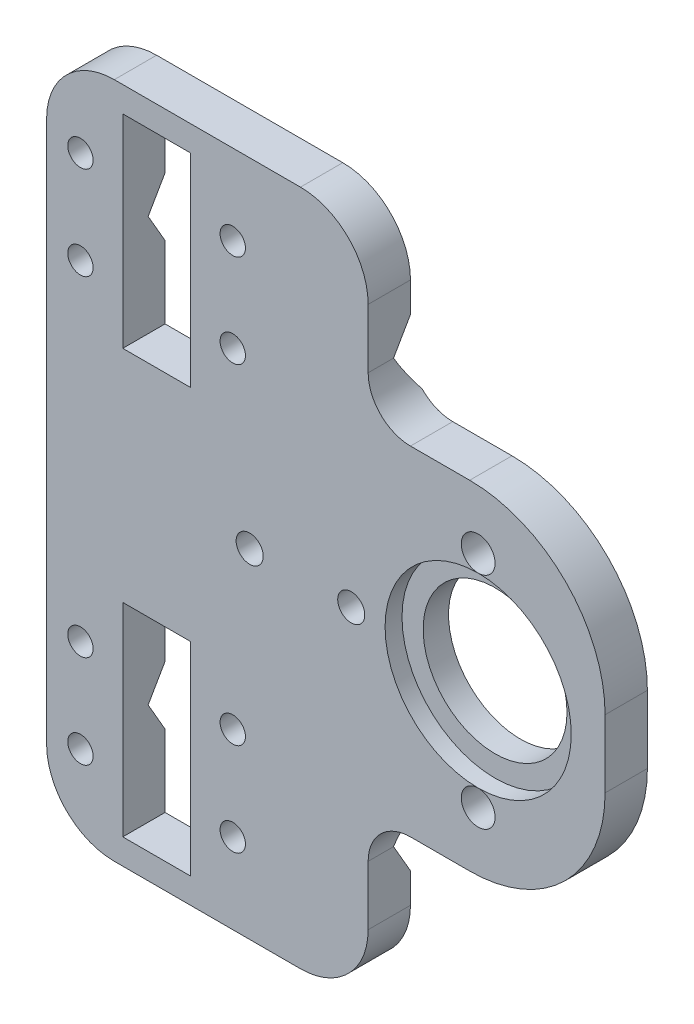
SolidWorks part; units mm, degrees
note: The reader was unsure of these and kept them because the rebuilt part matched: shared geometry of "Esboço6<3>".
material "Liga 1060"
ref_plane "Plano frontal" through (0, 0, 0) normal (0, 0, 1) x (1, 0, 0)
ref_plane "Plano superior" through (0, 0, 0) normal (0, 1, 0) x (1, 0, 0)
ref_plane "Plano direito" through (0, 0, 0) normal (1, 0, 0) x (0, 0, -1)
sketch "Esboço1" plane through (0, 0, 0) normal (0, 0, 1) x (1, 0, 0)
  line L0 (0, 0) -> (19, 0) construction
  line L1 (-19, 40) -> (19, 40)
  line L2 (-19, 40) -> (-19, -40)
  line L3 (-19, -40) -> (19, -40)
  line L4 (19, 40) -> (19, -40)
  line L5 (-19, 40) -> (19, -40) construction
  line L6 (-19, -40) -> (19, 40) construction
  line L7 (-10, 37) -> (-2, 37)
  line L8 (-10, 37) -> (-10, 13)
  line L9 (-10, 13) -> (-2, 13)
  line L10 (-2, 37) -> (-2, 13)
  line L11 (-10, 37) -> (-2, 13) construction
  line L12 (-10, 13) -> (-2, 37) construction
  line L13 (-10, -13) -> (-2, -37) construction
  line L14 (-10, -37) -> (-2, -13) construction
  line L15 (-2, -37) -> (-2, -13)
  line L16 (-10, -13) -> (-2, -13)
  line L17 (-10, -37) -> (-10, -13)
  line L18 (-10, -37) -> (-2, -37)
  line L21 (-6, 25) -> (-6, 13) construction
  line L22 (-20.4945, 25) -> (6.394, 25) construction
  line L23 (47, 20) -> (19, 20)
  line L24 (47, 20) -> (47, -20)
  line L25 (47, -20) -> (19, -20)
  line L26 (19, 20) -> (19, -20)
  line L27 (47, 20) -> (19, -20) construction
  line L28 (47, -20) -> (19, 20) construction
  circle A0 centre (-15, 19.5) radius 1.5
  circle A1 centre (-15, -19.5) radius 1.5
  circle A2 centre (3, -19.5) radius 1.5
  circle A3 centre (3, 19.5) radius 1.5
  circle A4 centre (3, 30.5) radius 1.5
  circle A5 centre (-15, 30.5) radius 1.5
  circle A6 centre (3, -30.5) radius 1.5
  circle A7 centre (-15, -30.5) radius 1.5
  point P0 (0, 0)
  point P5 (-6, 25)
  point P17 (-6, -25)
  point P30 (33, 0)
  dimension "D7" = 3
  dimension "D8" = 28
  dimension "D10" = 11
  dimension "D11" = 18
  dimension "D1" = 80
  dimension "D2" = 38
  dimension "D3" = 8
  dimension "D4" = 24
  dimension "D5" = 25
  dimension "D6" = 13
  dimension "D9" = 40
extrude "Ressalto-extrusão1" add sketch "Esboço1" along normal blind 5 contours L4 L1 L2 L3 A1 A0 L18 L17 L16 L15 L7 L10 L9 L8 A2 A3 | L25 L24 L23 L4
sketch "Esboço2" plane through (19, 0, 0) normal (1, 0, 0) x (0, 0, -1)
  line L0 (0, 25) -> (-2, 25) construction
  line L2 (-2, 25) -> (0, 28.4641)
  line L3 (0, 28.4641) -> (0, 21.5359)
  line L4 (-2, 25) -> (0, 21.5359)
  line L5 (0, 0) -> (-5, 0) construction
  line L7 (0, -25) -> (-2, -25) construction
  line L8 (-2, -25) -> (0, -21.5359)
  line L9 (0, -28.4641) -> (0, -21.5359)
  line L10 (-2, -25) -> (0, -28.4641)
  line L11 (0, 40) -> (0, 20) construction
  line L12 (0, 37) -> (0, 13) construction
  circle A0 centre (2.6188, 25) radius 4 construction
  point P2 (0, 28.1814)
  point P11 (0, 0)
  point P12 (0, 0)
  point P19 (0, 0)
  point P21 (0, 25)
  dimension "D2" = 8
  dimension "D1" = 120
  dimension "D3" = 2
extrude "Corte-extrusão1" cut sketch "Esboço2" against normal through all
hole_wizard "Escareado para parafuso com cabeça escareada elevada de M41" [suppressed] positions "Esboço4" profile "Esboço3" countersink size "M4" standard "Din"
sketch "Esboço4" plane through (0, 0, 0) normal (0, 0, -1) x (-1, 0, 0)
  line L7 (-34.5, 15.5) -> (-3.5, 15.5) construction
  line L10 (-3.5, 15.5) -> (-3.5, -15.5) construction
  line L11 (-3.5, -15.5) -> (-34.5, -15.5) construction
  line L12 (-34.5, -15.5) -> (-34.5, 15.5) construction
  line L14 (0, 0) -> (-34.5, 0) construction
  line L16 (-39, 20) -> (1, 20) construction
  line L17 (1, 20) -> (1, -20) construction
  line L18 (1, -20) -> (-39, -20) construction
  line L19 (-39, -20) -> (-39, 20) construction
  line L20 (-40, -50) -> (-40, 50) construction
  point P0 (-34.5, 15.5)
  point P20 (-3.5, 15.5)
  point P26 (-3.5, -15.5)
  point P28 (-34.5, -15.5)
  dimension "D1" = 31
  dimension "D2" = 4.5
  dimension "D3" = 1
sketch "Esboço3" plane through (34.5, 15.5, 0) normal (1, 0, 0) x (0, 1, 0)
  line L0 (0, 0) -> (0, 5)
  line L1 (0, 5) -> (2.275, 5)
  line L2 (2.25, 4.975) -> (2.25, 2.45)
  line L3 (2.25, 2.45) -> (4.7, 0)
  line L5 (4.7, 0) -> (0, 0)
  line L6 (-2.25, 2.45) -> (-4.7, 0) construction
  line L7 (2.275, 5) -> (2.25, 4.975)
  line L8 (-2.275, 5) -> (-2.25, 4.975) construction
  line L11 (0, -6.35) -> (0, 107.95) construction
  dimension "Thru Hole Dia." = 4.5
  dimension "Thru Hole Depth" = 5
  dimension "Near C'Sink Dia." = 9.4
  dimension "Near C'Sink Angle" = 90
  dimension "Far C'Sink Dia." = 4.55
  dimension "Far C'Sink Angle" = 90
sketch "Esboço5" [suppressed] plane through (0, 0, 5) normal (0, 0, 1) x (1, 0, 0)
  line L0 (3.5, 15.5) -> (34.5, -15.5) construction
  circle A0 centre (19, 0) radius 11.05
  dimension "D1" = 22.1
extrude "Corte-extrusão2" [suppressed] cut sketch "Esboço5" against normal through all
chamfer "Chanfro1" [suppressed] distance 1 angle 45
sketch "Esboço6" plane through (0, 0, 5) normal (0, 0, 1) x (1, 0, 0)
  line L0 (47, 0) -> (32, 0) construction
  line L2 (47, 20) -> (47, -20) construction
  circle A0 centre (32, 0) radius 11
  circle A1 centre (32, 0) radius 8.5
  dimension "D1" = 22
  dimension "D3" = 17
  dimension "D2" = 15
extrude "Corte-extrusão3" cut sketch "Esboço6" against normal through all
extrude "Corte-extrusão4" cut sketch "Esboço6<3>" against normal blind 2
sketch "Esboço6<3>" plane through (0, 0, 5) normal (0, 0, 1) x (1, 0, 0) same geometry as "Esboço6"
hole_wizard "Furo roscado de M41" positions "Esboço8" profile "Esboço7" tap size "M4" standard "Din" end condition through all
sketch "Esboço8" plane through (-8.2902, 15.8332, 5) normal (0, 0, 1) x (1, 0, 0)
  line L0 (40.2902, -15.8332) -> (40.2902, -2.8327) construction
  circle A0 centre (40.2902, -15.8332) radius 13.0005 construction
  point P0 (40.2902, -2.8327)
  point P14 (40.2902, -28.8337)
  dimension "D1" = 26.001
sketch "Esboço7" plane through (32, 13.0005, 5) normal (1, 0, 0) x (0, -1, 0)
  line L0 (0, 0) -> (0, 5)
  line L1 (0, 5) -> (2, 5)
  line L2 (2, 5) -> (2, 0)
  line L5 (2, 0) -> (0, 0)
  line L11 (0, -6.35) -> (0, 107.95) construction
  dimension "Thread Major Dia." = 4
  dimension "Thru Tap Drill Depth" = 5
fillet "Filete1" radius 16 2 edges at (47, -20, 2.5) (47, 20, 2.5)
fillet "Filete2" radius 5 2 edges at (19, -20, 2.5) (19, 20, 2.5)
fillet "Filete3" radius 8 4 edges at (-19, -40, 2.5) (19, -40, 2.5) (19, 40, 2.5) (-19, 40, 2.5)
sketch "Esboço9" plane through (0, 0, 0) normal (0, 0, 1) x (1, 0, 0)
  line L0 (-19, 0) -> (11, 0) construction
  line L1 (-19, 32) -> (-19, -32) construction
  line L2 (11, 0) -> (11, 6.7975) construction
  circle A0 centre (5, 0) radius 1.6
  circle A1 centre (17, 0) radius 1.6
  dimension "D1" = 3.2
  dimension "D2" = 12
  dimension "D3" = 30
extrude "Corte-extrusão9" cut sketch "Esboço9" along normal through all
